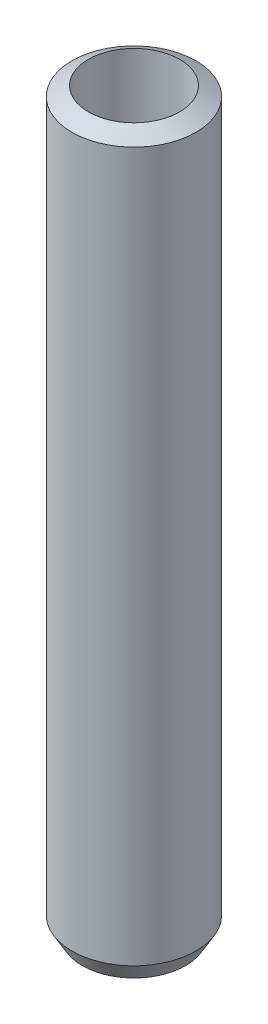
SolidWorks part; units mm, degrees
ref_plane "Front Plane" through (0, 0, 0) normal (0, 0, 1) x (1, 0, 0)
ref_plane "Top Plane" through (0, 0, 0) normal (0, 1, 0) x (1, 0, 0)
ref_plane "Right Plane" through (0, 0, 0) normal (1, 0, 0) x (0, 0, -1)
sketch "Sketch1" plane through (0, 0, 0) normal (0, 1, 0) x (1, 0, 0)
  circle A0 centre (0, 0) radius 12.5
  dimension "SHAFT_OD" = 25
extrude "Boss-Extrude1" add sketch "Sketch1" along normal blind 148.5928
sketch "Sketch2" plane through (0, 0, 0) normal (0, 1, 0) x (1, 0, 0)
  circle A0 centre (0, 0) radius 9.1923
  dimension "BORE_D" = 18.3846
extrude "Cut-Extrude1" cut sketch "Sketch2" along normal through all
chamfer "Chamfer1" distance 2.0696 angle 60 2 edges at (0, 148.5928, 12.5) (0, 0, 12.5) first distance on face at (0, 148.5928, 12.5) first distance on face at (0, 0, 9.1923)
